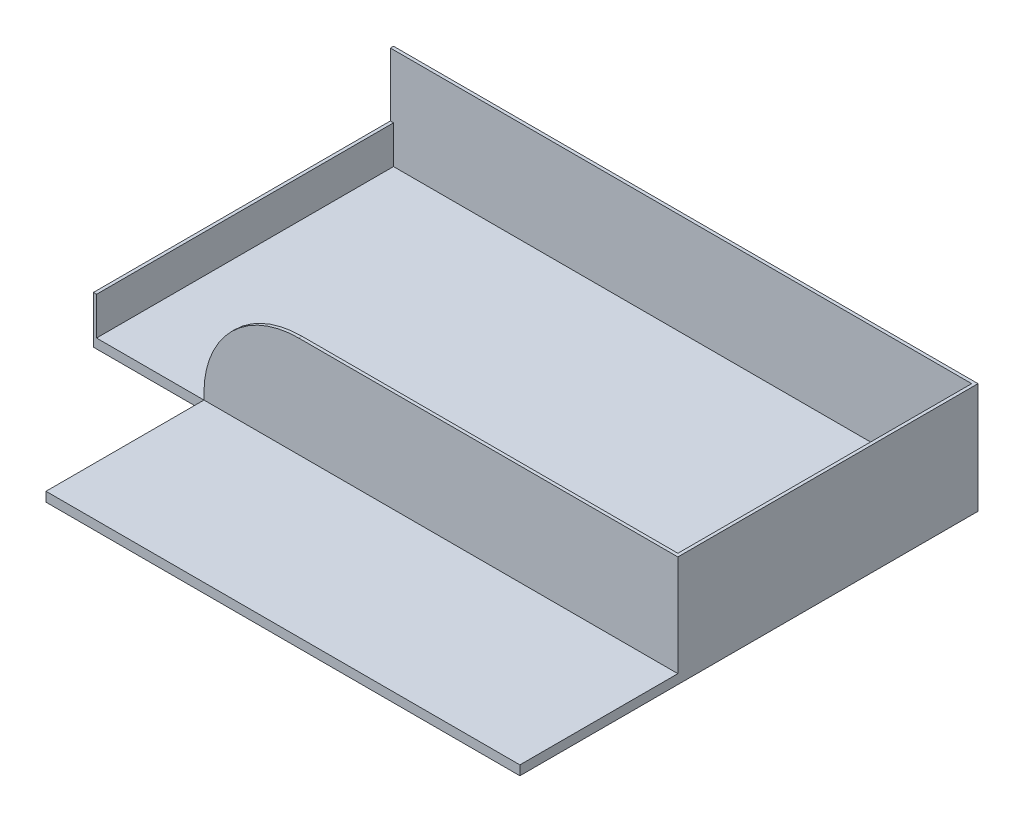
SolidWorks part; units mm, degrees
ref_plane "Front Plane" through (0, 0, 0) normal (0, 0, 1) x (1, 0, 0)
ref_plane "Top Plane" through (0, 0, 0) normal (0, 1, 0) x (1, 0, 0)
ref_plane "Right Plane" through (0, 0, 0) normal (1, 0, 0) x (0, 0, -1)
sketch "Sketch1" plane through (0, 0, 0) normal (0, 1, 0) x (1, 0, 0)
  line L0 (0, -10) -> (1840, -10)
  line L1 (0, 0) -> (1850, 0)
  line L2 (0, 0) -> (0, -950)
  line L3 (0, -950) -> (1850, -950)
  line L4 (1850, 0) -> (1850, -950)
  line L5 (1840, -10) -> (1840, -950)
  line L8 (350, -1450) -> (350, -950)
  line L9 (1850, -950) -> (0, -950)
  line L10 (1850, -950) -> (1850, -1450)
  line L11 (1850, -1450) -> (350, -1450)
  line L12 (10, -940) -> (1840, -940) construction
  line L13 (10, -10) -> (10, -940) construction
  line L14 (10, -10) -> (1840, -10) construction
  line L15 (1840, -10) -> (1840, -940) construction
  dimension "D1" = 1850
  dimension "D2" = 950
  dimension "D4" = 500
  dimension "D5" = 1500
  dimension "D3" = 10
extrude "Boss-Extrude1" add sketch "Sketch1" along normal blind 30 contours L2 L1 L4 L3
extrude "Boss-Extrude2" add sketch "Sketch1<3>" along normal blind 350 contours L4 L1 L2 L3 L0 L5 region at (20.7966, 0, 5)
sketch "Sketch1<3>" plane through (0, 0, 0) normal (0, 1, 0) x (1, 0, 0) same geometry as "Sketch1"
extrude "Boss-Extrude4" add sketch "Sketch1<4>" along normal blind 30 contours L3 L11 L10 region at (1100, 0, 1200)
sketch "Sketch1<4>" plane through (0, 0, 0) normal (0, 1, 0) x (1, 0, 0) same geometry as "Sketch1"
sketch "Sketch3" plane through (0, 0, 950) normal (0, 0, 1) x (1, 0, 0)
  line L1 (350, 30) -> (1850, 30)
  line L2 (350, 30) -> (350, 50)
  line L3 (650, 350) -> (1850, 350)
  line L4 (1850, 30) -> (1850, 350)
  arc A0 (350, 50) -> (650, 350) centre (650, 50) cw
  dimension "D1" = 300
extrude "Boss-Extrude5" add sketch "Sketch3" against normal blind 10
sketch "Sketch4" plane through (0, 0, 0) normal (-1, 0, 0) x (0, 0, 1)
  line L0 (0, 350) -> (0, 0) construction
  line L1 (950, 0) -> (0, 0)
  line L2 (950, 0) -> (950, 150)
  line L3 (950, 150) -> (0, 150)
  line L4 (0, 0) -> (0, 150)
  dimension "D1" = 150
extrude "Boss-Extrude6" add sketch "Sketch4" against normal blind 10
